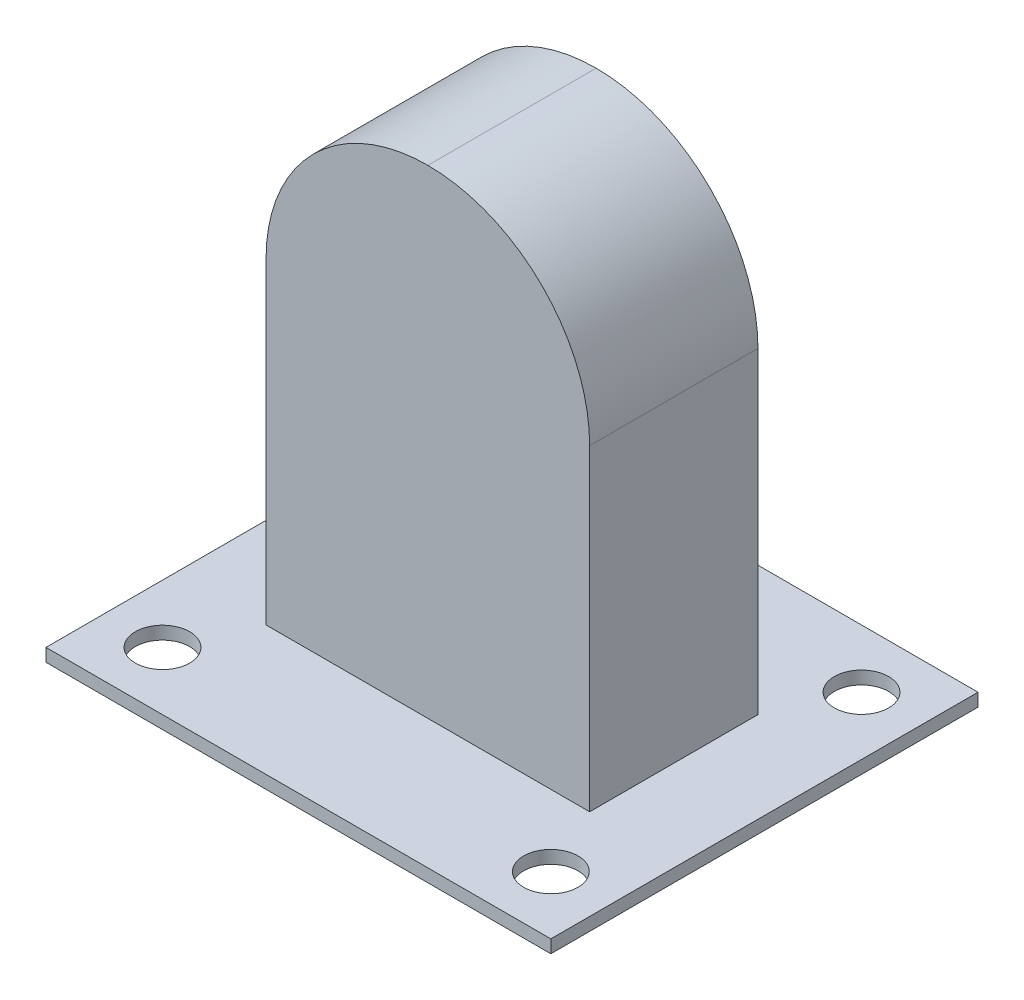
SolidWorks part; units mm, degrees
ref_plane "前视基准面" through (0, 0, 0) normal (0, 0, 1) x (1, 0, 0)
ref_plane "上视基准面" through (0, 0, 0) normal (0, 1, 0) x (1, 0, 0)
ref_plane "右视基准面" through (0, 0, 0) normal (1, 0, 0) x (0, 0, -1)
sketch "草图1" plane through (0, 0, 0) normal (0, 1, 0) x (1, 0, 0)
  line L0 (-19.5, 0) -> (19.5, 0) construction
  line L1 (-19.5, 16.5) -> (19.5, 16.5)
  line L2 (-19.5, 16.5) -> (-19.5, -16.5)
  line L3 (-19.5, -16.5) -> (19.5, -16.5)
  line L4 (19.5, 16.5) -> (19.5, -16.5)
  line L5 (-19.5, 16.5) -> (19.5, -16.5) construction
  line L6 (-19.5, -16.5) -> (19.5, 16.5) construction
  line L7 (-15, 12) -> (15, 12) construction
  line L8 (-15, 12) -> (-15, -12) construction
  line L9 (-15, -12) -> (15, -12) construction
  line L10 (15, 12) -> (15, -12) construction
  line L11 (-15, 12) -> (15, -12) construction
  line L12 (-15, -12) -> (15, 12) construction
  line L13 (0, 16.5) -> (0, -16.5) construction
  circle A0 centre (-15, 12) radius 2.1
  circle A1 centre (15, 12) radius 2.1
  circle A2 centre (15, -12) radius 2.1
  circle A3 centre (-15, -12) radius 2.1
  point P0 (0, 0)
  point P6 (0, 0)
  dimension "D5" = 4.2
  dimension "D1" = 39
  dimension "D2" = 33
  dimension "D3" = 30
  dimension "D4" = 24
extrude "凸台-拉伸1" add sketch "草图1" along normal blind 1
sketch "草图2" plane through (0, 0, 0) normal (0, 0, 1) x (1, 0, 0)
  line L0 (-19.5, 1) -> (19.5, 1) construction
  line L1 (-19.5, 1) -> (19.5, 1) construction
  line L2 (0, 38) -> (0, 1) construction
  line L3 (-12.5, 1) -> (12.5, 1)
  line L4 (-12.5, 1) -> (-12.5, 38)
  line L5 (-12.5, 38) -> (12.5, 38)
  line L6 (12.5, 1) -> (12.5, 38)
  dimension "D1" = 37
  dimension "D2" = 25
extrude "凸台-拉伸2" add sketch "草图2" along normal mid plane 13
fillet "圆角1" radius 12.5 2 edges at (-12.5, 38, 0) (12.5, 38, 0)
